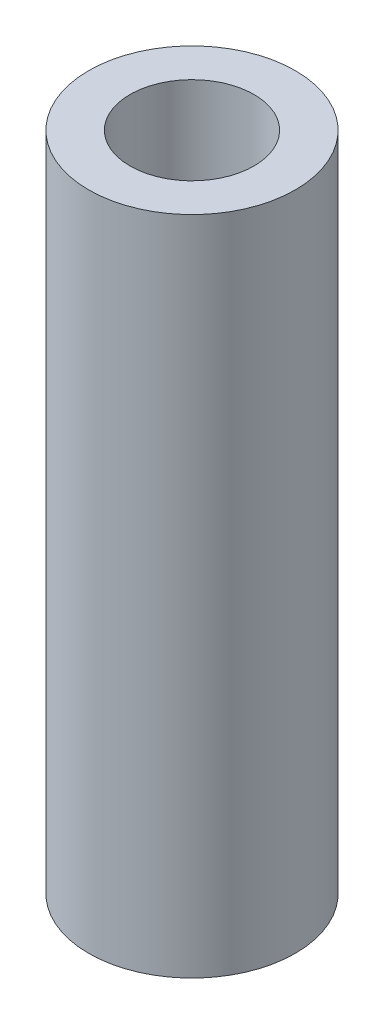
SolidWorks part; units mm, degrees
note: The reader was unsure of these and kept them because the rebuilt part matched: shared geometry of "Sketch1<3>".
material "AISI 4130 Steel, annealed at 865C"
ref_plane "X-Y Datum" through (0, 0, 0) normal (0, 0, 1) x (1, 0, 0)
ref_plane "X-Z Datum" through (0, 0, 0) normal (0, 1, 0) x (1, 0, 0)
ref_plane "Y-Z Datum" through (0, 0, 0) normal (1, 0, 0) x (0, 0, -1)
sketch "Sketch1" plane through (0, 0, 0) normal (0, 1, 0) x (1, 0, 0)
  circle A0 centre (0, 0) radius 7.9375
  circle A1 centre (0, 0) radius 4.7625
  dimension "D1" = 15.875
  dimension "D2" = 9.525
extrude "Boss-Extrude1" add sketch "Sketch1" against normal blind 50.8 contours A0
extrude "Cut-Extrude1" cut sketch "Sketch1<3>" against normal offset from surface (44.45 mm away) 6.35 contours A1 up to face at (0, -50.8, 7.9375)
sketch "Sketch1<3>" plane through (0, 0, 0) normal (0, 1, 0) x (1, 0, 0) same geometry as "Sketch1"
hole_wizard "1/4 Clearance Hole1" [suppressed] positions "Sketch2" profile "Sketch3" hole size "1/4" standard "ANSI Inch"
sketch "Sketch2" plane through (0, -50.8, 0) normal (0, -1, 0) x (-1, 0, 0)
  point P0 (0, 0)
sketch "Sketch3" plane through (0, -50.8, 0) normal (1, 0, 0) x (0, 0, -1)
  line L0 (0, 0) -> (0, 50.8)
  line L1 (0, 50.8) -> (3.2639, 50.8)
  line L2 (3.2639, 50.8) -> (3.2639, 0)
  line L5 (3.2639, 0) -> (0, 0)
  line L11 (0, -6.35) -> (0, 107.95) construction
  dimension "Thru Hole Dia." = 6.5278
  dimension "Thru Hole Depth" = 50.8
